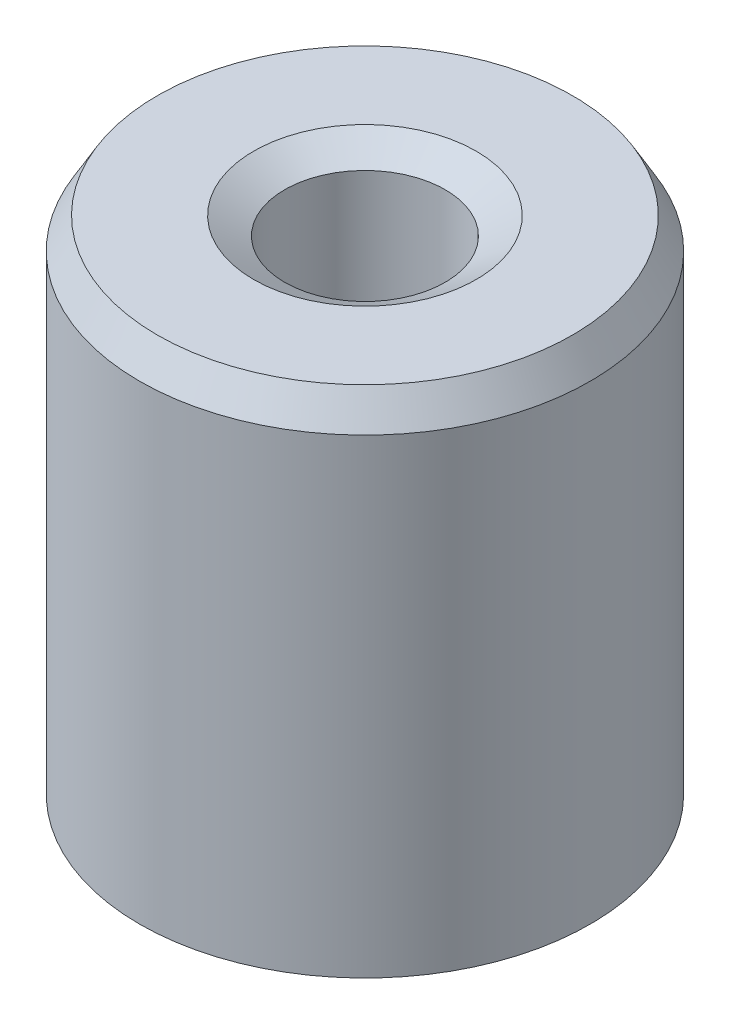
SolidWorks part; units mm, degrees
ref_plane "Front Plane" through (0, 0, 0) normal (0, 0, 1) x (1, 0, 0)
ref_plane "Top Plane" through (0, 0, 0) normal (0, 1, 0) x (1, 0, 0)
ref_plane "Right Plane" through (0, 0, 0) normal (1, 0, 0) x (0, 0, -1)
sketch "Sketch1" plane through (0, 0, 0) normal (0, 1, 0) x (1, 0, 0)
  circle A0 centre (0, 0) radius 7.5
  dimension "SLEEVE_OD" = 15
extrude "Boss-Extrude1" add sketch "Sketch1" along normal blind 17.2737
sketch "Sketch2" plane through (0, 0, 0) normal (0, 1, 0) x (1, 0, 0)
  circle A0 centre (0, 0) radius 2.6717
  dimension "BORE_D" = 5.3435
extrude "Cut-Extrude1" cut sketch "Sketch2" along normal through all
chamfer "Chamfer1" distance 1.0309 angle 30 4 edges at (0, 17.2737, 2.6717) (0, 0, 2.6717) (0, 0, 7.5) (0, 17.2737, 7.5) first distance on face at (0, 17.2737, 2.6717) first distance on face at (0, 0, 2.6717) first distance on face at (0, 17.2737, 7.5)
